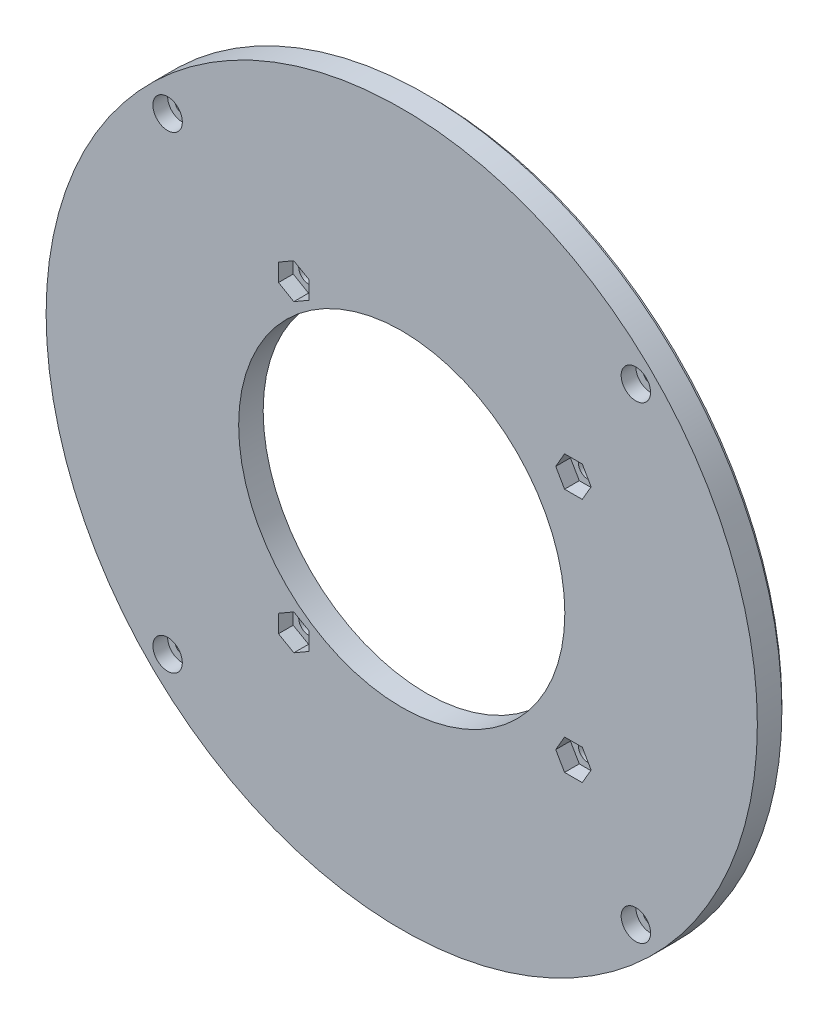
SolidWorks part; units mm, degrees
material "ABS"
ref_plane "Ebene vorne" through (0, 0, 0) normal (0, 0, 1) x (1, 0, 0)
ref_plane "Ebene oben" through (0, 0, 0) normal (0, 1, 0) x (1, 0, 0)
ref_plane "Ebene rechts" through (0, 0, 0) normal (1, 0, 0) x (0, 0, -1)
sketch "Skizze1" plane through (0, 0, 0) normal (0, 0, 1) x (1, 0, 0)
  circle A0 centre (0, 0) radius 72.5
  circle A1 centre (0, 0) radius 33.25
  dimension "D1" = 145
  dimension "D2" = 66.5
extrude "Lidar Top Base" add sketch "Skizze1" along normal blind 5
hole_wizard "Lidar Screws" positions "Skizze2" profile "Skizze3" hole size "Ø4.0" standard "ISO" end condition through all
sketch "Skizze2" plane through (0, 0, 5) normal (0, 0, 1) x (1, 0, 0)
  line L0 (0, 0) -> (0, 72.5) construction
  line L2 (-72.5, 0) -> (72.5, 0) construction
  circle A0 centre (0, 0) radius 72.5 construction
  point P0 (-22, 31)
  point P2 (35, 25)
  point P4 (35, -25)
  point P6 (-22, -31)
  point P24 (31.4997, 0)
  point P31 (31, 22)
  point P32 (0, 0)
  point P33 (0, 0)
  point P34 (0, 0)
  point P35 (0, 0)
  dimension "D1" = 35
  dimension "D2" = 25
  dimension "D3" = 22
  dimension "D4" = 31
sketch "Skizze3" plane through (-22, 31, 5) normal (1, 0, 0) x (0, -1, 0)
  line L0 (0, 0) -> (0, 5)
  line L1 (0, 5) -> (2, 5)
  line L2 (2, 5) -> (2, 0)
  line L5 (2, 0) -> (0, 0)
  line L11 (0, -6.35) -> (0, 107.95) construction
  dimension "Bohrerdurchmesser" = 4
  dimension "Bohrungstiefe" = 5
hole_wizard "Spacer Screws" positions "Skizze4" profile "Skizze5" counterbore size "M1.6" standard "DIN" end condition through all
sketch "Skizze4" plane through (0, 0, 5) normal (0, 0, -1) x (-1, 0, 0)
  line L1 (47.7297, 47.7297) -> (-47.7297, 47.7297) construction
  line L2 (-47.7297, 47.7297) -> (-47.7297, -47.7297) construction
  line L3 (-47.7297, -47.7297) -> (47.7297, -47.7297) construction
  line L4 (47.7297, -47.7297) -> (47.7297, 47.7297) construction
  circle A0 centre (0, 0) radius 47.7297 construction
  point P0 (47.7297, 47.7297)
  point P2 (47.7297, -47.7297)
  point P4 (-47.7297, -47.7297)
  point P6 (-47.7297, 47.7297)
  point P18 (0, 0)
  point P19 (0, 0)
  point P20 (0, 0)
  point P21 (0, 0)
  dimension "D1" = 67.5
sketch "Skizze5" plane through (-47.7297, 47.7297, 5) normal (1, 0, 0) x (0, -1, 0)
  line L0 (0, 0) -> (0, 5)
  line L1 (0, 5) -> (1.5, 5)
  line L3 (1.5, 5) -> (1.5, 3)
  line L4 (1.5, 3) -> (3, 3)
  line L5 (3, 3) -> (3, 0)
  line L7 (3, 0) -> (0, 0)
  line L11 (0, -6.35) -> (0, 107.95) construction
  dimension "Bohrerdurchmesser" = 3
  dimension "Bohrungstiefe" = 5
  dimension "Senkdurchmesser2" = 6
  dimension "Senktiefe2" = 3
sketch "Skizze6" plane through (0, 0, 0) normal (0, 0, -1) x (-1, 0, 0)
  line L0 (70.5, 0) -> (-72.5, 0) construction
  line L1 (-47.7297, 47.7297) -> (-35, 25) construction
  line L2 (22, 31) -> (47.7297, 47.7297) construction
  line L3 (-47.3739, 52.2107) -> (-30.8203, 22.6532)
  line L4 (-51.0784, 48.5927) -> (-33.8448, 17.8211)
  line L5 (19.939, 32.6419) -> (48.4711, 51.1938)
  line L6 (24.3175, 29.5249) -> (52.0464, 47.5544)
  line L7 (-38.49, 23.0455) -> (-34.6528, 16.194)
  line L8 (-31.51, 26.9545) -> (-29.8259, 23.9474)
  line L9 (-50.7834, 46.0195) -> (-51.7958, 47.8272)
  line L10 (-44.676, 49.4399) -> (-46.6102, 52.8936)
  line L11 (45.8218, 50.664) -> (47.7177, 51.8967)
  line L12 (49.6376, 44.7954) -> (52.7239, 46.8022)
  line L13 (-70.5, 0) -> (-57.4564, 0)
  line L14 (38.25, 0) -> (70.5, 0)
  line L15 (70.4929, 1) -> (38.2369, 1)
  circle A0 centre (0, 0) radius 70.5
  circle A1 centre (0, 0) radius 72.5 construction
  circle A2 centre (0, 0) radius 33.25
  circle A3 centre (0, 0) radius 33.25 construction
  circle A4 centre (-46.4564, 0) radius 11
  circle A5 centre (-35, -25) radius 2 construction
  circle A6 centre (0, 0) radius 38.25
  arc A7 (-44.676, 49.4399) -> (-50.7834, 46.0195) centre (-47.7297, 47.7297) cw
  arc A8 (-38.49, 23.0455) -> (-31.51, 26.9545) centre (-35, 25) cw
  arc A9 (18.7537, 33.3371) -> (25.2777, 28.7072) centre (22, 31) cw
  arc A10 (49.6376, 44.7954) -> (45.8218, 50.664) centre (47.7297, 47.7297) cw
  dimension "D1" = 2
  dimension "D2" = 22
  dimension "D4" = 2.2064
  dimension "D5" = 5
  dimension "D8" = 8
  dimension "D10" = 7
  dimension "D11" = 4
  dimension "D3" = 27.5
  dimension "D6" = 5
  dimension "D7" = 5
  dimension "D9" = 7
  dimension "D12" = 1
extrude "Bottom Structure" cut sketch "Skizze6" against normal offset from surface (4.5 mm away) 0.5 contours L7 A8 L4 A7 L9 A0 L13 A4 A6 | L5 A10 L11 A0 L10 A7 L3 A8 L8 A6 A9 | L12 A10 L6 A9 A6 L14 A0 | A6 A4 | A4 A6 region at (2.5401, 50.9171, 0) region at (53.82, 21.1426, 0) region at (47.1246, 0, 0) region at (-49.9075, 21.074, 0) region at (37.0069, 0, 0) up to face at (-44.7297, 47.7297, 5)
sketch "Skizze9" plane through (0, 0, 5) normal (0, 0, 1) x (1, 0, 0)
  line L1 (-18.875, 32.8042) -> (-22, 34.6084)
  line L2 (-22, 34.6084) -> (-25.125, 32.8042)
  line L3 (-25.125, 32.8042) -> (-25.125, 29.1958)
  line L4 (-25.125, 29.1958) -> (-22, 27.3916)
  line L5 (-22, 27.3916) -> (-18.875, 29.1958)
  line L6 (-18.875, 29.1958) -> (-18.875, 32.8042)
  line L7 (38.6084, 25) -> (36.8042, 28.125)
  line L8 (36.8042, 28.125) -> (33.1958, 28.125)
  line L9 (33.1958, 28.125) -> (31.3916, 25)
  line L10 (31.3916, 25) -> (33.1958, 21.875)
  line L11 (33.1958, 21.875) -> (36.8042, 21.875)
  line L12 (36.8042, 21.875) -> (38.6084, 25)
  circle A0 centre (-22, 31) radius 3.125 construction
  circle A1 centre (35, 25) radius 3.125 construction
  dimension "D1" = 6.25
extrude "Hex Nut" cut sketch "Skizze9" against normal blind 3
mirror "Structure Mirror" about plane through (0, 0, 0) normal (0, 1, 0) of "Hex Nut", "Bottom Structure"
sketch "Skizze7" plane through (0, 0, 0) normal (0, 0, -1) x (-1, 0, 0)
  circle A0 centre (0, 0) radius 71
  circle A1 centre (0, 0) radius 71.5
  circle A4 centre (0, 0) radius 72.5 construction
  dimension "D1" = 0.5
  dimension "D2" = 1
extrude "Cover Ring" add sketch "Skizze7" along normal blind 1
